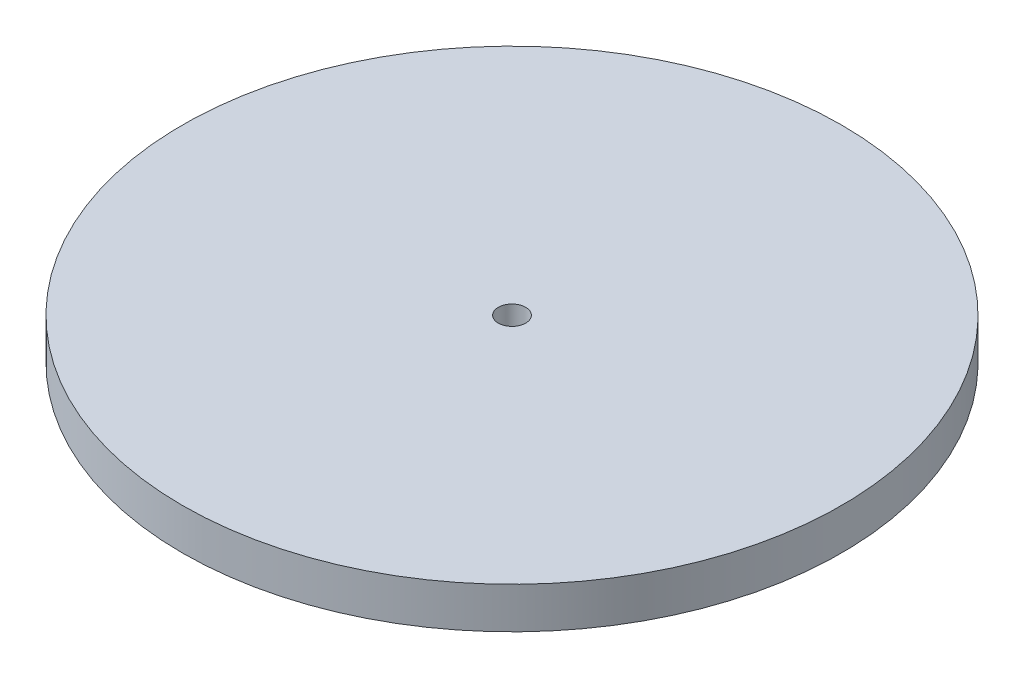
SolidWorks part; units mm, degrees
material "6061-T4 (SS)"
ref_plane "Front Plane" through (0, 0, 0) normal (0, 0, 1) x (1, 0, 0)
ref_plane "Top Plane" through (0, 0, 0) normal (0, 1, 0) x (1, 0, 0)
ref_plane "Right Plane" through (0, 0, 0) normal (1, 0, 0) x (0, 0, -1)
sketch "Sketch1" plane through (0, 0, 0) normal (0, 1, 0) x (1, 0, 0)
  circle A0 centre (0, 0) radius 76.2
  circle A1 centre (0, 0) radius 3.175
  dimension "D1" = 152.4
  dimension "D2" = 6.35
extrude "Boss-Extrude1" add sketch "Sketch1" along normal blind 9.525
